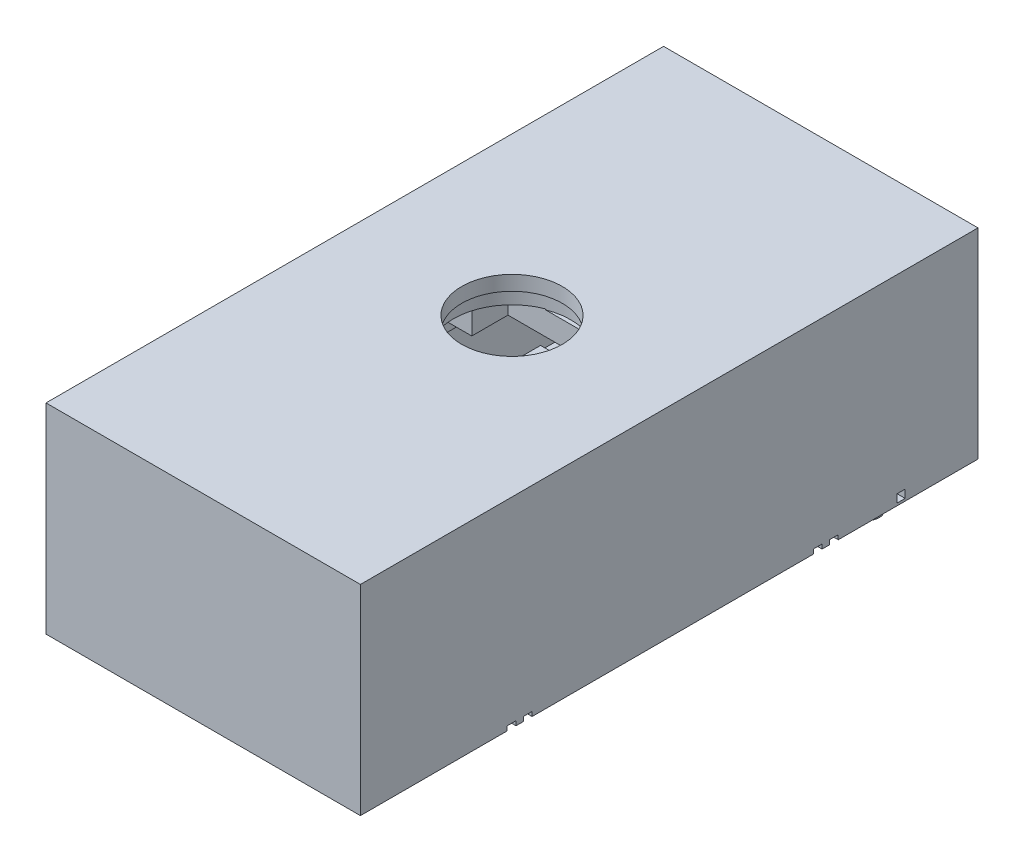
SolidWorks part; units mm, degrees
ref_plane "Front Plane" through (0, 0, 0) normal (0, 0, 1) x (1, 0, 0)
ref_plane "Top Plane" through (0, 0, 0) normal (0, 1, 0) x (1, 0, 0)
ref_plane "Right Plane" through (0, 0, 0) normal (1, 0, 0) x (0, 0, -1)
other "Configuration Table"
sketch "Sketch1" plane through (0, 0, 0) normal (0, 1, 0) x (1, 0, 0)
  line L1 (-19.55, 39.5) -> (19.55, 39.5)
  line L2 (-19.55, 39.5) -> (-19.55, -37.3)
  line L3 (-19.55, -37.3) -> (19.55, -37.3)
  line L4 (19.55, 39.5) -> (19.55, -37.3)
extrude "Block" add sketch "Sketch1" along normal blind 24.9023 from offset 4.7
sketch "Sketch2" plane through (0, 0, 0) normal (0, 1, 0) x (1, 0, 0)
  line L1 (-17.45, 32.7) -> (17.45, 32.7)
  line L2 (-17.45, 32.7) -> (-17.45, -20.8)
  line L3 (-17.45, -20.8) -> (17.45, -20.8)
  line L4 (17.45, 32.7) -> (17.45, -20.8)
extrude "Cell pocket" cut sketch "Sketch2" along normal blind 11.86 from offset 7.14
sketch "Sketch3" plane through (0, 0, 0) normal (0, 1, 0) x (1, 0, 0)
  line L1 (-17.45, 32.7) -> (17.45, 32.7)
  line L2 (-17.45, 32.7) -> (-17.45, 22.1)
  line L3 (-17.45, 22.1) -> (17.45, 22.1)
  line L4 (17.45, 32.7) -> (17.45, 22.1)
extrude "Cell protection-board end" cut sketch "Sketch3" along normal blind 0.54 from offset 6.6
sketch "Sketch4" plane through (0, 0, 0) normal (0, 1, 0) x (1, 0, 0)
  line L1 (-18.45, 4.75) -> (-9.2, 4.75)
  line L2 (-18.45, 4.75) -> (-18.45, -1.75)
  line L3 (-18.45, -1.75) -> (-9.2, -1.75)
  line L4 (-9.2, 4.75) -> (-9.2, -1.75)
  line L6 (9.4, 23.82) -> (18.45, 23.82)
  line L7 (9.4, 23.82) -> (9.4, 17.32)
  line L8 (9.4, 17.32) -> (18.45, 17.32)
  line L9 (18.45, 23.82) -> (18.45, 17.32)
  line L11 (9.2, -14.25) -> (18.45, -14.25)
  line L12 (9.2, -14.25) -> (9.2, -20.75)
  line L13 (9.2, -20.75) -> (18.45, -20.75)
  line L14 (18.45, -14.25) -> (18.45, -20.75)
extrude "S1-S3 and plug pockets" cut sketch "Sketch4" along normal blind 1.9 from offset 4.7
sketch "Sketch5" plane through (0, 0, 0) normal (0, 1, 0) x (1, 0, 0)
  line L1 (-9.1, 37.5) -> (8.4, 37.5)
  line L2 (-9.1, 37.5) -> (-9.1, 26.8)
  line L3 (-9.1, 26.8) -> (8.4, 26.8)
  line L4 (8.4, 37.5) -> (8.4, 26.8)
extrude "J4 and flex entry" cut sketch "Sketch5" along normal blind 1.9 from offset 4.7
sketch "Sketch6" plane through (0, 0, 0) normal (0, 1, 0) x (1, 0, 0)
  line L1 (-9.1, 37.5) -> (8.4, 37.5)
  line L2 (-9.1, 37.5) -> (-9.1, 32.7)
  line L3 (-9.1, 32.7) -> (8.4, 32.7)
  line L4 (8.4, 37.5) -> (8.4, 32.7)
extrude "J4 flex riser" cut sketch "Sketch6" along normal blind 20.19 from offset 4.7
sketch "Sketch7" plane through (0, 0, 0) normal (0, 1, 0) x (1, 0, 0)
  line L1 (-9.1, 37.5) -> (8.4, 37.5)
  line L2 (-9.1, 37.5) -> (-9.1, 16.6)
  line L3 (-9.1, 16.6) -> (8.4, 16.6)
  line L4 (8.4, 37.5) -> (8.4, 16.6)
extrude "Flex channel over the cells" cut sketch "Sketch7" along normal blind 5.89 from offset 19
sketch "Sketch8" plane through (0, 0, 0) normal (0, 1, 0) x (1, 0, 0)
  line L1 (-12.8, 17.2) -> (12.8, 17.2)
  line L2 (-12.8, 17.2) -> (-12.8, -7.3)
  line L3 (-12.8, -7.3) -> (12.8, -7.3)
  line L4 (12.8, 17.2) -> (12.8, -7.3)
extrude "Camera board pocket" cut sketch "Sketch8" along normal blind 3.5823 from offset 19
sketch "Sketch9" plane through (0, 0, 0) normal (0, 1, 0) x (1, 0, 0)
  line L1 (-7.3, 7.9) -> (7.3, 7.9)
  line L2 (-7.3, 7.9) -> (-7.3, -5.7)
  line L3 (-7.3, -5.7) -> (7.3, -5.7)
  line L4 (7.3, 7.9) -> (7.3, -5.7)
extrude "Holder pocket" cut sketch "Sketch9" along normal blind 3.1 from offset 22.4823
sketch "Sketch10" plane through (0, 0, 0) normal (0, 1, 0) x (1, 0, 0)
  line L1 (-11.3, 3.4) -> (11.3, 3.4)
  line L2 (-11.3, 3.4) -> (-11.3, -1.2)
  line L3 (-11.3, -1.2) -> (11.3, -1.2)
  line L4 (11.3, 3.4) -> (11.3, -1.2)
extrude "Holder ear pocket" cut sketch "Sketch10" along normal blind 3.1 from offset 22.4823
sketch "Sketch11" plane through (0, 0, 0) normal (0, 1, 0) x (1, 0, 0)
  line L1 (-9.1, 17.9) -> (9.1, 17.9)
  line L2 (-9.1, 17.9) -> (-9.1, 12.1)
  line L3 (-9.1, 12.1) -> (9.1, 12.1)
  line L4 (9.1, 17.9) -> (9.1, 12.1)
extrude "Camera FFC pocket" cut sketch "Sketch11" along normal blind 2.4077 from offset 22.4823
sketch "Sketch12" plane through (0, 0, 0) normal (0, 1, 0) x (1, 0, 0)
  circle A0 centre (0, 1.1) radius 7.3
extrude "Barrel hole" cut sketch "Sketch12" along normal blind 2.3 from offset 25.4823
sketch "Sketch13" plane through (0, 0, 0) normal (0, 1, 0) x (1, 0, 0)
  circle A0 centre (0, 1.1) radius 6.25
extrude "Lens thread hole" cut sketch "Sketch13" along normal through all from offset 27.6823
sketch "Sketch14" plane through (0, 0, 0) normal (0, 1, 0) x (1, 0, 0)
  circle A0 centre (10.5, 7.52) radius 0.8
  circle A1 centre (-10.5, 7.52) radius 0.8
  circle A2 centre (10.5, -4.98) radius 0.8
  circle A3 centre (-10.5, -4.98) radius 0.8
extrude "Camera screw pilots" cut sketch "Sketch14" along normal blind 4.6 from offset 22.4823
sketch "Sketch15" plane through (0, 0, 0) normal (0, 1, 0) x (1, 0, 0)
  line L1 (-19.75, 3.05) -> (-18.15, 3.05)
  line L2 (-19.75, 3.05) -> (-19.75, 1.95)
  line L3 (-19.75, 1.95) -> (-18.15, 1.95)
  line L4 (-18.15, 3.05) -> (-18.15, 1.95)
  line L6 (-19.75, 1.05) -> (-18.15, 1.05)
  line L7 (-19.75, 1.05) -> (-19.75, -0.05)
  line L8 (-19.75, -0.05) -> (-18.15, -0.05)
  line L9 (-18.15, 1.05) -> (-18.15, -0.05)
  line L11 (18.15, 22.12) -> (19.75, 22.12)
  line L12 (18.15, 22.12) -> (18.15, 21.02)
  line L13 (18.15, 21.02) -> (19.75, 21.02)
  line L14 (19.75, 22.12) -> (19.75, 21.02)
  line L16 (18.15, 20.12) -> (19.75, 20.12)
  line L17 (18.15, 20.12) -> (18.15, 19.02)
  line L18 (18.15, 19.02) -> (19.75, 19.02)
  line L19 (19.75, 20.12) -> (19.75, 19.02)
  line L21 (18.15, -15.95) -> (19.75, -15.95)
  line L22 (18.15, -15.95) -> (18.15, -17.05)
  line L23 (18.15, -17.05) -> (19.75, -17.05)
  line L24 (19.75, -15.95) -> (19.75, -17.05)
  line L26 (18.15, -17.95) -> (19.75, -17.95)
  line L27 (18.15, -17.95) -> (18.15, -19.05)
  line L28 (18.15, -19.05) -> (19.75, -19.05)
  line L29 (19.75, -17.95) -> (19.75, -19.05)
extrude "Probe wire half-slots" cut sketch "Sketch15" along normal blind 0.55 from offset 4.7
sketch "Sketch16" plane through (0, 0, 0) normal (0, 1, 0) x (1, 0, 0)
  circle A0 centre (15.32, 29.94) radius 1.5
extrude "Mic tube" add sketch "Sketch16" against normal blind 2.9 from offset 4.7
sketch "Sketch17" plane through (0, 0, 0) normal (0, 1, 0) x (1, 0, 0)
  circle A0 centre (15.32, 29.94) radius 0.5
extrude "Mic bore" cut sketch "Sketch17" along normal blind 4.3 from offset 1.7
sketch "Sketch18" plane through (0, 0, 0) normal (0, 1, 0) x (1, 0, 0)
  line L1 (14.82, 30.44) -> (19.75, 30.44)
  line L2 (14.82, 30.44) -> (14.82, 29.44)
  line L3 (14.82, 29.44) -> (19.75, 29.44)
  line L4 (19.75, 30.44) -> (19.75, 29.44)
extrude "Mic duct" cut sketch "Sketch18" along normal blind 1 from offset 5
